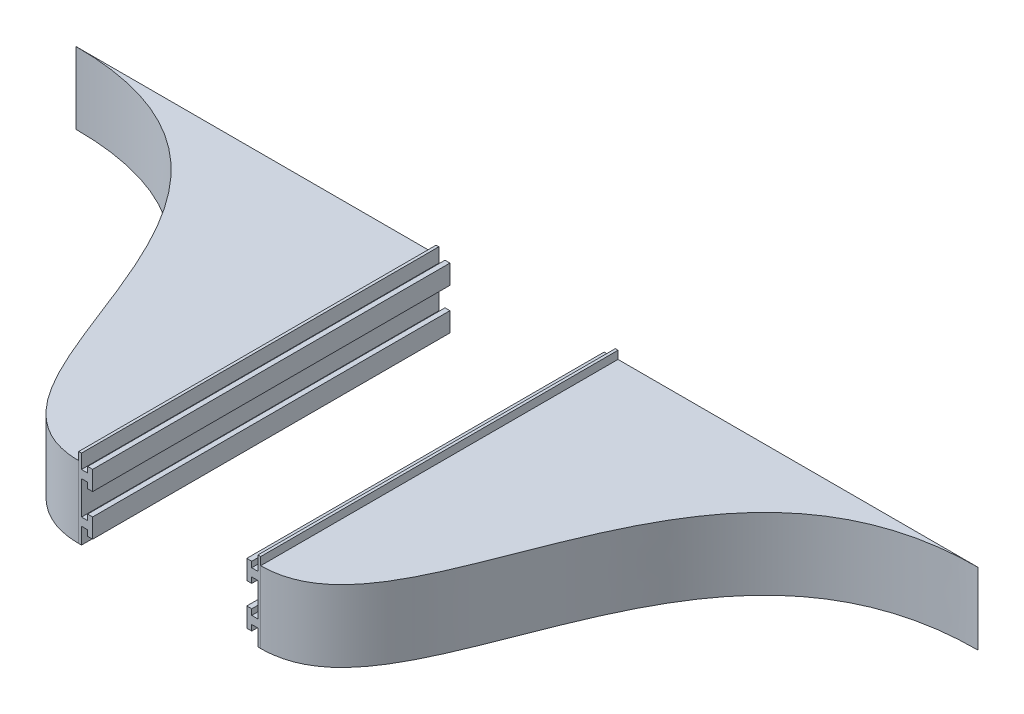
SolidWorks part; units mm, degrees
material "PLA"
ref_plane "Front Plane" through (0, 0, 0) normal (0, 0, 1) x (1, 0, 0)
ref_plane "Top Plane" through (0, 0, 0) normal (0, 1, 0) x (1, 0, 0)
ref_plane "Right Plane" through (0, 0, 0) normal (1, 0, 0) x (0, 0, -1)
sketch "Sketch1" plane through (0, 0, 101.3276) normal (0, 0, 1) x (1, 0, 0)
  line L440 (-32.1, -15.0497) -> (-32.1, -21)
  line L441 (-29.8428, -15.0497) -> (-32.1, -15.0497)
  line L442 (-29.8428, -17.1189) -> (-29.8428, -15.0497)
  line L443 (-28.0428, -17.1189) -> (-29.8428, -17.1189)
  line L444 (-28.0428, -10.1) -> (-28.0428, -17.1189)
  line L445 (-29.8428, -10.1) -> (-28.0428, -10.1)
  line L446 (-29.8428, -12.1692) -> (-29.8428, -10.1)
  line L447 (-32.1, -12.1692) -> (-29.8428, -12.1692)
  line L448 (-32.1, -0.0497) -> (-32.1, -12.1692)
  line L449 (-29.8428, -0.0497) -> (-32.1, -0.0497)
  line L450 (-29.8428, -2.1189) -> (-29.8428, -0.0497)
  line L451 (-28.0428, -2.1189) -> (-29.8428, -2.1189)
  line L452 (-28.0428, 4.9) -> (-28.0428, -2.1189)
  line L453 (-29.8428, 4.9) -> (-28.0428, 4.9)
  line L454 (-29.8428, 2.8308) -> (-29.8428, 4.9)
  line L455 (-32.1, 2.8308) -> (-29.8428, 2.8308)
  line L456 (-32.1, 8) -> (-32.1, 2.8308)
  line L457 (-32.1, -15.0497) -> (-32.1, -21)
  line L458 (-29.8428, -15.0497) -> (-32.1, -15.0497)
  line L459 (-29.8428, -17.1189) -> (-29.8428, -15.0497)
  line L460 (-28.0428, -17.1189) -> (-29.8428, -17.1189)
  line L461 (-28.0428, -10.1) -> (-28.0428, -17.1189)
  line L462 (-29.8428, -10.1) -> (-28.0428, -10.1)
  line L463 (-29.8428, -12.1692) -> (-29.8428, -10.1)
  line L464 (-32.1, -12.1692) -> (-29.8428, -12.1692)
  line L465 (-32.1, -0.0497) -> (-32.1, -12.1692)
  line L466 (-29.8428, -0.0497) -> (-32.1, -0.0497)
  line L467 (-29.8428, -2.1189) -> (-29.8428, -0.0497)
  line L468 (-28.0428, -2.1189) -> (-29.8428, -2.1189)
  line L469 (-28.0428, 4.9) -> (-28.0428, -2.1189)
  line L470 (-29.8428, 4.9) -> (-28.0428, 4.9)
  line L471 (-29.8428, 2.8308) -> (-29.8428, 4.9)
  line L472 (-32.1, 2.8308) -> (-29.8428, 2.8308)
  line L473 (-32.1, 8) -> (-32.1, 2.8308)
  line L474 (-32.1, -21) -> (-33.1, -21)
  line L475 (-33.1, -21) -> (-33.1, 8)
  line L476 (-33.1, 8) -> (-32.1, 8)
  dimension "D1" = 0.1
extrude "Boss-Extrude1" add sketch "Sketch1" along normal up to surface (130 mm away)
sketch "Sketch2" plane through (75.2969, -0.8945, -218.7008) normal (0, 1, 0) x (1, 0, 0)
  line L0 (-108.3969, -450.0284) -> (-108.3969, -320.0284)
  line L2 (-239.3767, -320.0284) -> (-108.3969, -320.0284) construction
  line L4 (-108.3969, -320.0284) -> (-107.3969, -320.0284) construction
  line L5 (-239.3767, -320.0284) -> (-108.3969, -320.0284)
  line L9 (-108.3969, -450.0284) -> (-162.4556, -450.0284) construction
  line L10 (-162.4556, -450.0284) -> (-139.7802, -320.0284) construction
  line L11 (-139.7802, -320.0284) -> (-239.3767, -320.0284) construction
  line L15 (-108.3969, -450.0284) -> (-108.3969, -320.0284) construction
  spline S0 degree 3 poles (-108.3969, -450.0284) (-162.4556, -450.0284) (-139.7802, -320.0284) (-239.3767, -320.0284) knots 0 0 0 0 1 1 1 1
  point P3 (-234.2034, -268.4184)
extrude "Boss-Extrude2" add sketch "Sketch2" along normal blind 6 and the other way up to surface (20.1055 mm away) other way up to face at (-32.6, -21, 166.3276)
mirror "Mirror1" about plane through (0, 0, 0) normal (1, 0, 0) of bodies 102
